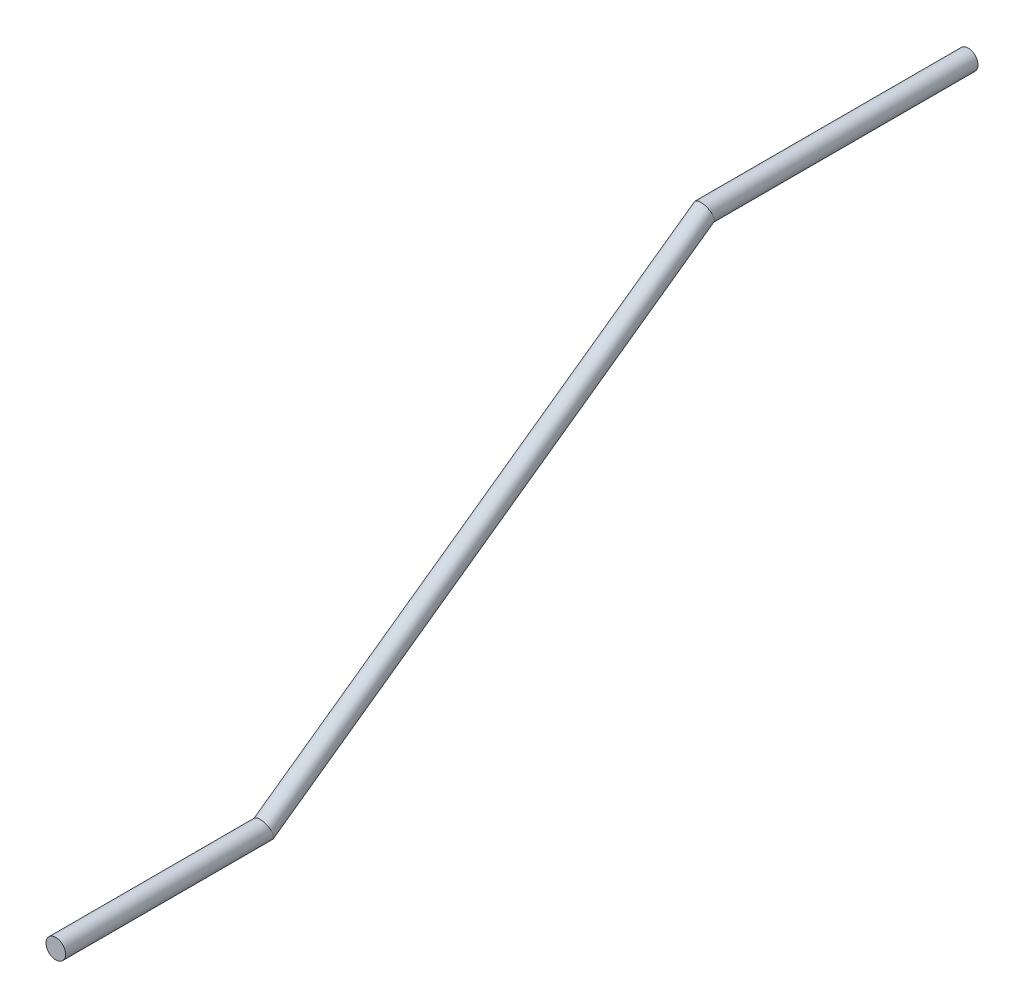
SolidWorks part; units mm, degrees
ref_plane "Front Plane" through (0, 0, 0) normal (0, 0, 1) x (1, 0, 0)
ref_plane "Top Plane" through (0, 0, 0) normal (0, 1, 0) x (1, 0, 0)
ref_plane "Right Plane" through (0, 0, 0) normal (1, 0, 0) x (0, 0, -1)
sketch3d "Route through both anchors"
  line L0 (15, 25.9808, -16.2) -> (15, 25.9808, 0)
  line L1 (15, 25.9808, 0) -> (13.9077, 5.6191, 25.9599)
  line L2 (13.9077, 5.6191, 25.9599) -> (13.9077, 5.6191, 38.7099)
sweep "Round TPU cord - 1.2 mm" add path "Route through both anchors" circular profile diameter 1.2 parameters "D3"=1.2
